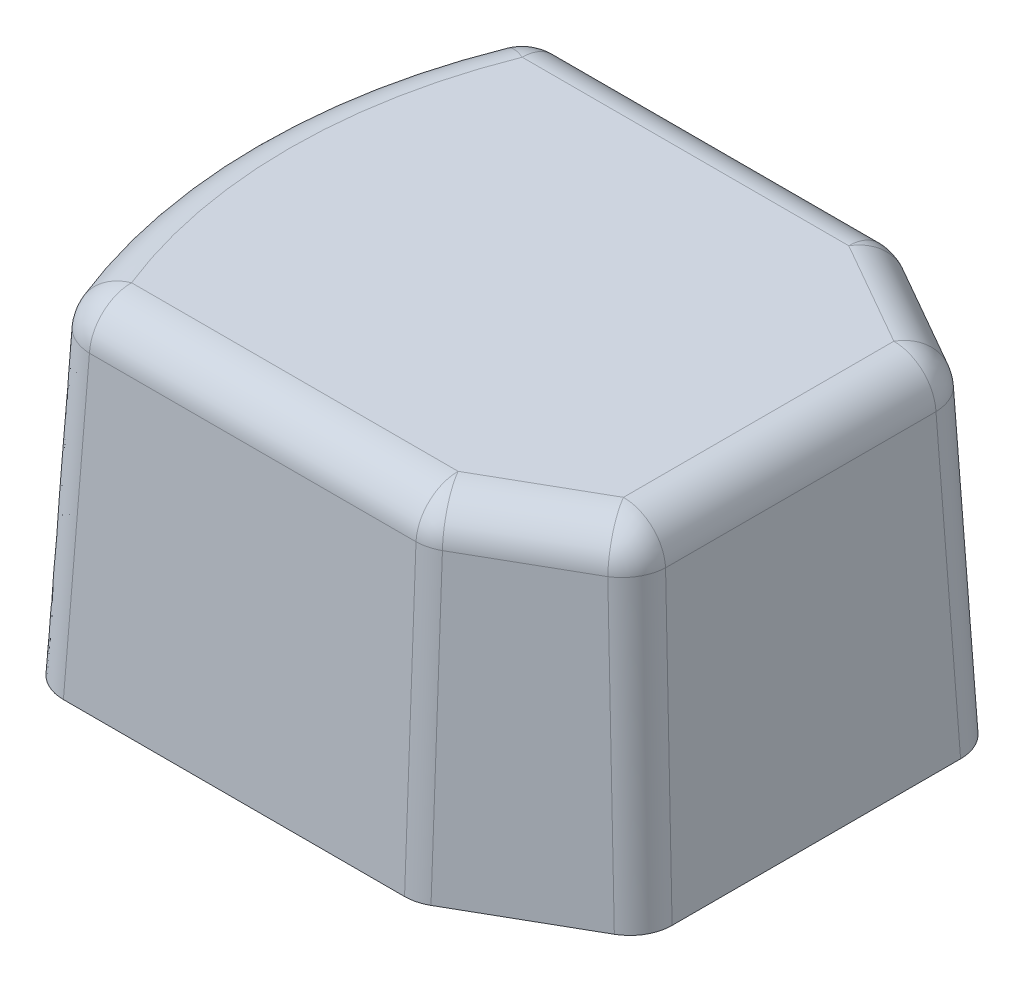
SolidWorks part; units mm, degrees
ref_plane "Front" through (0, 0, 0) normal (0, 0, 1) x (1, 0, 0)
ref_plane "Top" through (0, 0, 0) normal (0, 1, 0) x (1, 0, 0)
ref_plane "Right" through (0, 0, 0) normal (1, 0, 0) x (0, 0, -1)
sketch "Sketch1" plane through (0, 0, 0) normal (0, 1, 0) x (1, 0, 0)
  line L0 (-58.6146, 67.5) -> (-58.6146, -67.5) construction
  line L2 (-62.5, -60) -> (-62.5, 60)
  line L5 (-62.5, -60) -> (62.5, 60) construction
  line L6 (-62.5, 60) -> (62.5, -60) construction
  line L7 (62.5, 0) -> (-58.6146, 0) construction
  line L8 (-62.5, 60) -> (27.5, 60)
  line L9 (27.5, 60) -> (62.5, 40)
  line L10 (62.5, 40) -> (62.5, -40)
  line L12 (27.5, -60) -> (-62.5, -60)
  line L13 (27.5, 60) -> (62.5, 60) construction
  line L14 (62.5, 60) -> (62.5, 40) construction
  line L15 (27.5, -60) -> (62.5, -60) construction
  line L16 (62.5, -60) -> (62.5, -40) construction
  line L17 (27.5, -60) -> (62.5, -40)
  arc A0 (-58.6146, 67.5) -> (-58.6146, -67.5) centre (62.5, 0) ccw
  point P0 (0, 0)
  dimension "D3" = 135
  dimension "D1" = 125
  dimension "D2" = 120
  dimension "D4" = 35
  dimension "D5" = 20
  dimension "D6" = 20
extrude "Boss-Extrude1" add sketch "Sketch1" along normal blind 80 draft 3 contours L2 A0 | L2 region at (-67.9854, 0, 0) region at (-2.4883, 0, 0)
sketch "Sketch3" plane through (0, 0, 0) normal (0, -1, 0) x (1, 0, 0)
  line L0 (-62.5, 60) -> (27.5, 60) construction
  line L1 (27.5, 60) -> (62.5, 40) construction
  line L2 (62.5, 40) -> (62.5, -40) construction
  line L3 (62.5, -40) -> (27.5, -60) construction
  line L4 (27.5, -60) -> (-62.5, -60) construction
  line L5 (-62.5, -60) -> (-62.5, 60) construction
  line L6 (-57.4728, 58.5) -> (27.1017, 58.5)
  line L7 (27.1017, 58.5) -> (57.5, 41.1295)
  line L8 (57.5, 41.1295) -> (57.5, -41.1295)
  line L9 (57.5, -41.1295) -> (27.1017, -58.5)
  line L10 (27.1017, -58.5) -> (-57.4728, -58.5)
  line L11 (-57.4728, -58.5) -> (-57.4728, 58.5) construction
  arc A0 (-62.5, 60) -> (-62.5, -60) centre (62.5, 0) ccw construction
  arc A1 (-57.4728, 58.5) -> (-57.4728, -58.5) centre (57.5, 0) ccw
  dimension "D6" = 129
  dimension "D1" = 3
  dimension "D2" = 10
  dimension "D3" = 3
  dimension "D4" = 3
  dimension "D5" = 3
extrude "Cut-Extrude1" cut sketch "Sketch3" against normal blind 70 draft 3
fillet "Fillet1" radius 10 12 edges at (42.347, 80, 46.6872) (58.3074, 80, 0) (42.347, 80, -46.6872) (-16.7234, 80, -55.8074) (-71.9616, 80, 0) (-16.7234, 80, 55.8074) (60.4037, 40, 38.7835) (26.9433, 40, 57.9037) (60.4037, 40, -38.7835) (26.9433, 40, -57.9037)
sketch "Sketch4" plane through (0, 0, 0) normal (0, -1, 0) x (1, 0, 0)
  line L0 (-76.1542, 0) -> (62.5, 0) construction
  line L1 (62.5, -34.2047) -> (62.5, 34.2047) construction
  line L2 (-76.1542, 0) -> (-65.2509, -53.8954) construction
  line L3 (58.5, -25) -> (61.5, -25)
  line L4 (58.5, -25) -> (58.5, -34)
  line L5 (58.5, -34) -> (61.5, -34)
  line L6 (61.5, -25) -> (61.5, -34)
  line L7 (-68.4903, -29.0573) -> (-66.7057, -37.8786)
  line L8 (-66.7057, -37.8786) -> (-70.1362, -38.5726)
  line L9 (-70.1362, -38.5726) -> (-71.9208, -29.7513)
  line L10 (-71.9208, -29.7513) -> (-68.4903, -29.0573)
  line L11 (-68.4903, 29.0573) -> (-66.7057, 37.8786)
  line L12 (-66.7057, 37.8786) -> (-70.1362, 38.5726)
  line L13 (-70.1362, 38.5726) -> (-71.9208, 29.7513)
  line L14 (-71.9208, 29.7513) -> (-68.4903, 29.0573)
  line L15 (58.5, 34) -> (61.5, 34)
  line L16 (58.5, 25) -> (58.5, 34)
  line L17 (58.5, 25) -> (61.5, 25)
  line L18 (61.5, 25) -> (61.5, 34)
  arc A0 (-65.2509, 53.8954) -> (-65.2509, -53.8954) centre (62.5, 0) ccw construction
  point P16 (-70.2056, -29.4043)
  dimension "D1" = 1
  dimension "D2" = 25
  dimension "D3" = 9
  dimension "D4" = 3
  dimension "D5" = 9
  dimension "D6" = 3.5
  dimension "D7" = 30
extrude "Cut-Extrude2" cut sketch "Sketch4" against normal blind 5 draft 5
sketch "Sketch7" plane through (0, 0, 0) normal (0, -1, 0) x (1, 0, 0)
  line L0 (-56.0499, 60) -> (-56.0499, -60) construction
  line L1 (24.848, 60) -> (-56.0499, 60) construction
  line L2 (-76.1542, 0) -> (62.5, 0) construction
  line L3 (62.5, -34.2047) -> (62.5, 34.2047) construction
  line L4 (-58.0499, 51.1529) -> (-61.5669, 58.3384) construction
  line L5 (-58.0499, 51.1529) -> (-56.0499, 51.1529) construction
  arc A0 (-65.2509, 53.8954) -> (-65.2509, -53.8954) centre (62.5, 0) ccw construction
  circle A1 centre (-58.0499, 51.1529) radius 5
  circle A3 centre (-58.0499, -51.1529) radius 5
  spline S4 degree 3 poles (-56.0499, 60) (-57.0332, 60) (-57.9924, 59.858) (-59.1617, 59.5063) (-59.395, 59.4266) (-59.8521, 59.2515) (-60.0763, 59.156) (-60.7358, 58.8463) (-61.1584, 58.6088) (-61.9692, 58.072) (-62.3602, 57.7696) (-63.0859, 57.1177) (-63.422, 56.768) (-64.0417, 56.0218) (-64.3259, 55.6242) (-64.8365, 54.7848) (-65.0598, 54.3484) (-65.2509, 53.8954) knots 0 0 0 0 0.25 0.25 0.3125 0.3125 0.375 0.375 0.5 0.5 0.625 0.625 0.75 0.75 0.875 0.875 1 1 1 1 construction
  dimension "D2" = 10
  dimension "D1" = 2
  dimension "D3" = 8
  dimension "D4" = 8.8471
extrude "Cut-Extrude3" cut sketch "Sketch7" against normal blind 7
